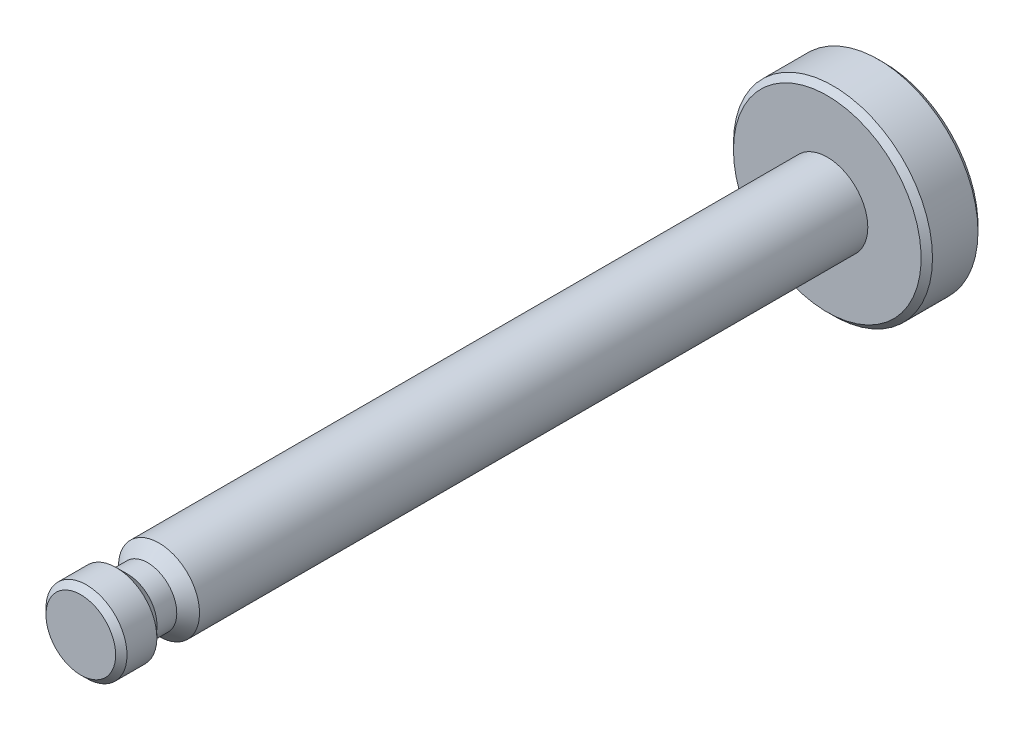
SolidWorks part; units mm, degrees
ref_plane "Front" through (0, 0, 0) normal (0, 0, 1) x (1, 0, 0)
ref_plane "Top" through (0, 0, 0) normal (0, 1, 0) x (1, 0, 0)
ref_plane "Right" through (0, 0, 0) normal (1, 0, 0) x (0, 0, -1)
sketch "Sketch2" plane through (0, 0, 0) normal (0, 0, 1) x (1, 0, 0)
  circle A0 centre (0, 0) radius 1.425
  dimension "D1" = 2.85
extrude "Shaft" add sketch "Sketch2" along normal blind 26.25
sketch "Sketch3" plane through (0, 0, 0) normal (0, 0, -1) x (-1, 0, 0)
  circle A3 centre (0, 0) radius 3.5
  dimension "D1" = 7
extrude "Head" add sketch "Sketch3" along normal blind 2
sketch "Sketch4" plane through (0, 0, 0) normal (1, 0, 0) x (0, 0, -1)
  line L0 (0, 0) -> (-24.25, 0) construction
  line L1 (-24.25, 0) -> (-24.25, 4.3666) construction
  line L2 (-25, 1.425) -> (-23.5, 1.425)
  line L3 (0, 1.425) -> (-26.25, 1.425) construction
  line L6 (-23.5, 1.425) -> (-23.9, 1.025)
  line L7 (-23.9, 1.025) -> (-24.6, 1.025)
  line L8 (-24.6, 1.025) -> (-25, 1.425)
  dimension "D1" = 24.25
  dimension "D2" = 1.5
  dimension "D3" = 45
  dimension "D4" = 0.4
revolve "e-Clip Notch" cut sketch "Sketch4" angle 360 about L0
chamfer "Deburs" distance 0.2 angle 45 3 edges at (1.425, 0, 26.25) (-3.5, 0, 0) (-3.5, 0, -2)
equation "\"D1@Shaft\"=\"Hardware Length@Box Assy.Assembly\"+6.25mm"
equation "\"D1@Sketch4\"=\"Hardware Length@Box Assy.Assembly\" + 4.25mm"
equation "\"D1@Sketch2\"=\"Hardware Clearance Hole Diameter@Box Assy.Assembly\"-.3"
